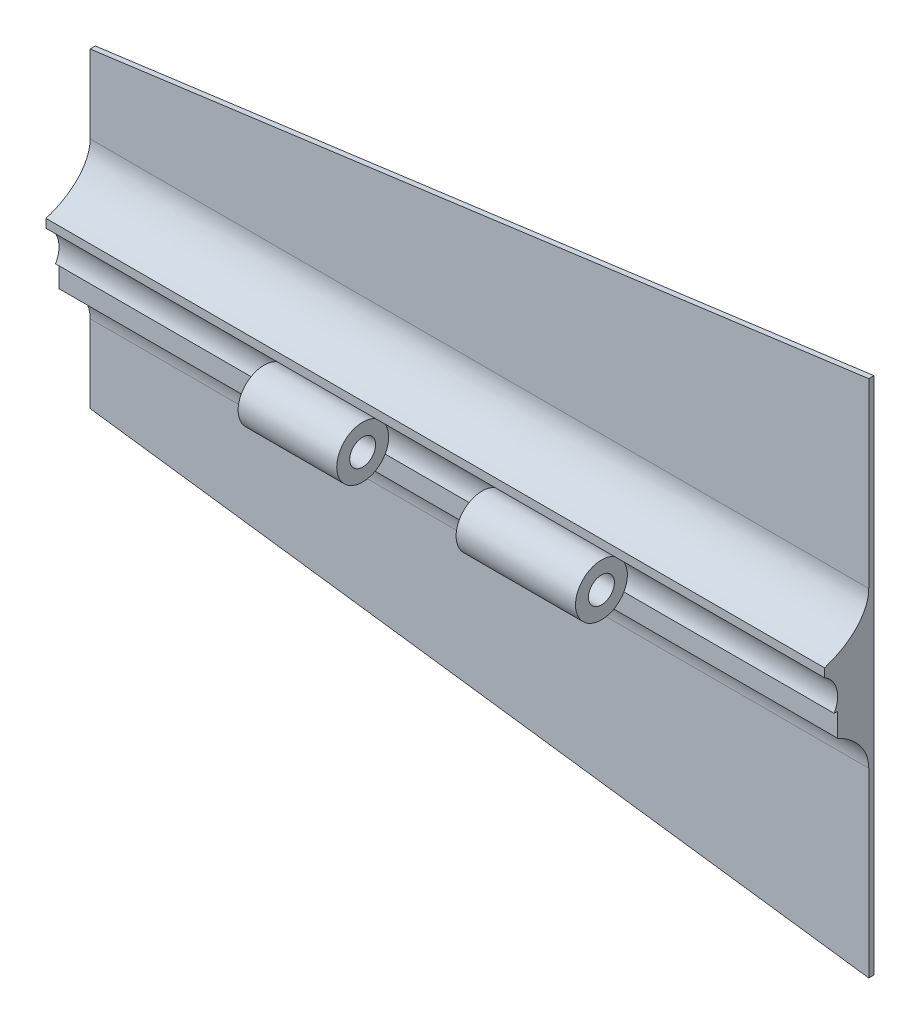
SolidWorks part; units mm, degrees
note: The reader was unsure of these and kept them because the rebuilt part matched: shared geometry of "Sketch9<3>".
ref_plane "Ön Düzlem" through (0, 0, 0) normal (0, 0, 1) x (1, 0, 0)
ref_plane "Üst Düzlem" through (0, 0, 0) normal (0, 1, 0) x (1, 0, 0)
ref_plane "Sağ Düzlem" through (0, 0, 0) normal (1, 0, 0) x (0, 0, -1)
sketch "Sketch1" plane through (0, 0, 0) normal (0, 0, 1) x (1, 0, 0)
  line L0 (75, 50) -> (75, -50)
  line L5 (75, -50) -> (-75, -30)
  line L6 (-75, -30) -> (-75, 30)
  line L7 (-75, 30) -> (75, 50)
  dimension "D1" = 60
  dimension "D2" = 100
  dimension "D3" = 30
  dimension "D4" = 50
  dimension "D5" = 150
  dimension "D6" = 75
extrude "Boss-Extrude1" add sketch "Sketch1" along normal blind 1
sketch "Sketch2" plane through (0, 0, 1) normal (0, 0, 1) x (1, 0, 0)
  line L0 (-75, 30) -> (-75, -30) construction
  line L1 (-75, 5) -> (139, 5)
  line L2 (-75, 5) -> (-75, -5)
  line L3 (-75, -5) -> (139, -5)
  line L4 (139, 5) -> (139, -5)
  dimension "D1" = 214
  dimension "D2" = 5
  dimension "D3" = 10
extrude "Boss-Extrude5" add sketch "Sketch2" along normal blind 100 and the other way blind 1
fillet "Fillet3" radius 15 2 edges at (0, -5, 1) (0, 5, 1) second distance 10 first distance on face at (46.3333, -5, 34) first distance on face at (46.3333, 5, 34)
sketch "Sketch6" plane through (-75, 0, 0) normal (-1, 0, 0) x (0, 0, 1)
  line L0 (9.5, 6.9868) -> (9.5, 4.3301)
  line L1 (14.5, 6.9868) -> (14.5, 4.3301)
  line L2 (14.5, -4.3301) -> (14.5, -7.2979)
  line L3 (9.5, -4.3301) -> (9.5, -7.2979)
  line L4 (9.5, 6.9868) -> (14.5, 6.9868)
  line L5 (14.5, -7.2979) -> (9.5, -7.2979)
  arc A0 (9.5, 4.3301) -> (9.5, -4.3301) centre (12, 0) ccw
  arc A1 (14.5, -4.3301) -> (14.5, 4.3301) centre (12, 0) ccw
  dimension "D1" = 10
  dimension "D2" = 12
  dimension "D3" = 5
  dimension "D4" = 2.5
extrude "Cut-Extrude2" cut sketch "Sketch6" against normal blind 229
sketch "Sketch7" plane through (0, 0, 0) normal (0, 0, -1) x (-1, 0, 0)
  line L0 (-75, 5) -> (-75, -5)
  line L1 (-75, -5) -> (-139, -5)
  line L2 (-139, -5) -> (-139, 5)
  line L3 (-139, 5) -> (-75, 5)
extrude "Cut-Extrude3" cut sketch "Sketch7" against normal blind 14
sketch "Sketch8" plane through (0, -5, 0) normal (0, -1, 0) x (-1, 0, 0)
  line L0 (83.1047, -11.7495) -> (-144.8648, -11.7495)
surface "Surface-Extrude1" sketch "Sketch8" parameters "D1"=64, "D2"=72
split "Split1" trimming surface bodies 112 bodies to split 109 resulting bodies 113
delete or keep bodies "Body-Delete/Keep 1" type delete bodies bodies 113
sketch "Sketch9" plane through (75, 0, 0) normal (1, 0, 0) x (0, 0, -1)
  circle A0 centre (-12, 0) radius 5
extrude "Extrude-Thin2" add sketch "Sketch9" against normal blind 23 from offset 40.5 thin contours A0 thin type one direction reverse wall 2.5 offset against normal yes
extrude "Extrude-Thin3" add sketch "Sketch9<3>" against normal blind 19 from offset 86.5 thin thin type one direction reverse wall 2.5 offset against normal yes
sketch "Sketch9<3>" plane through (75, 0, 0) normal (1, 0, 0) x (0, 0, -1) same geometry as "Sketch9"
sketch "Sketch10" plane through (0, 0, 0) normal (0, 0, -1) x (-1, 0, 0)
  line L0 (-75, 0) -> (75, 0) construction
  line L1 (-75, -50) -> (-75, 50) construction
  line L2 (75, 30) -> (75, -30) construction
  line L3 (75, -15) -> (75, -5.9871) construction
sketch "Sketch12" plane through (-30.5, 0, 0) normal (-1, 0, 0) x (0, 0, 1)
  line L0 (7, -2.5) -> (7.6699, -2.5)
  line L2 (7, -2.5) -> (7, -7.6904)
  line L4 (7, -7.6904) -> (9.5, -7.6904)
  line L5 (9.5, -7.6904) -> (9.5, -4.3301)
  arc A0 (7.6699, -2.5) -> (9.5, -4.3301) centre (12, 0) ccw
extrude "Cut-Extrude8" cut sketch "Sketch12" against normal blind 153 and the other way blind 71 contours A0 L5 L4 L2 L0
sketch "Sketch13" plane through (-75, 0, 0) normal (-1, 0, 0) x (0, 0, 1)
